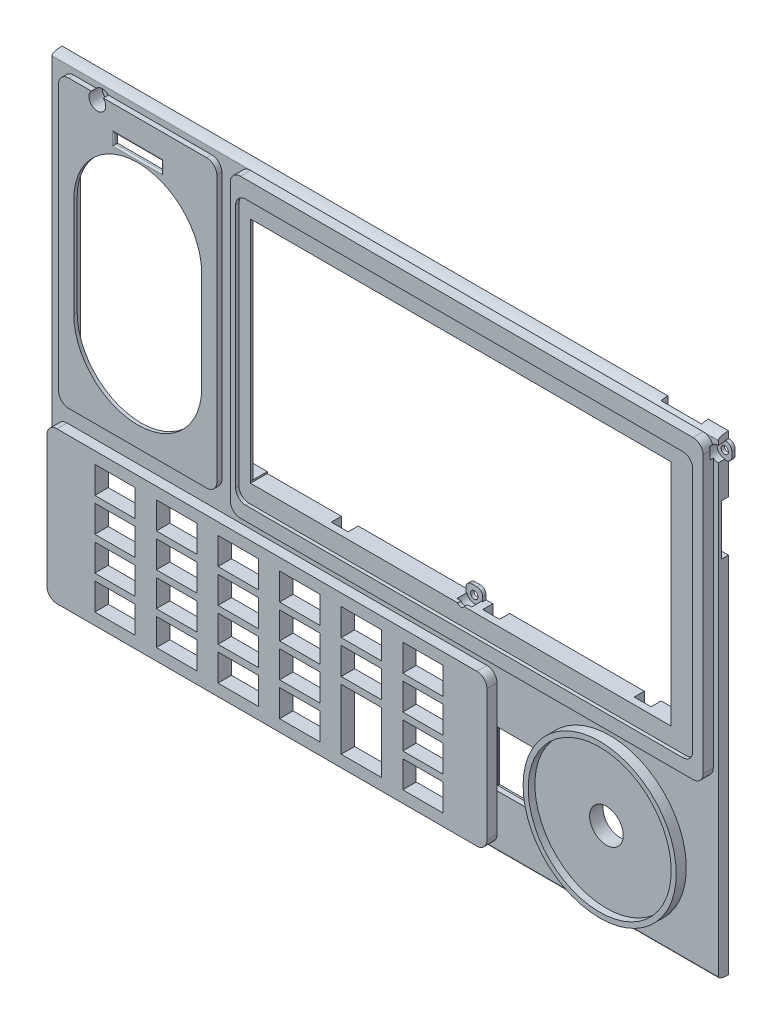
SolidWorks part; units mm, degrees
ref_plane "Front Plane" through (0, 0, 0) normal (0, 0, 1) x (1, 0, 0)
ref_plane "Top Plane" through (0, 0, 0) normal (0, 1, 0) x (1, 0, 0)
ref_plane "Right Plane" through (0, 0, 0) normal (1, 0, 0) x (0, 0, -1)
sketch "Sketch1" plane through (0, 0, 0) normal (0, 0, 1) x (1, 0, 0)
  line L1 (99, -70) -> (-99, -70)
  line L2 (99, -70) -> (99, 70)
  line L3 (99, 70) -> (-99, 70)
  line L4 (-99, -70) -> (-99, 70)
  line L5 (99, -70) -> (-99, 70) construction
  line L6 (99, 70) -> (-99, -70) construction
  point P0 (0, 0)
  dimension "D1" = 198
  dimension "D2" = 140
extrude "main_body" add sketch "Sketch1" along normal blind 3
fillet "long_corners" radius 3 2 edges at (0, 70, 3) (0, -70, 3) second distance 1 first distance on face at (0, 70, 1.5) first distance on face at (0, -70, 1.5)
sketch "Sketch2" plane through (0, 0, 3) normal (0, 0, 1) x (1, 0, 0)
  line L0 (-99, 24.75) -> (99, 24.75) construction
  line L1 (-99, 69) -> (-99, -69) construction
  line L2 (99, -69) -> (99, 69) construction
  line L3 (99, 69) -> (-99, 69) construction
  line L4 (-48.5, -17.75) -> (-95.5, -17.75)
  line L5 (-48.5, -17.75) -> (-48.5, 67.25)
  line L6 (-48.5, 67.25) -> (-95.5, 67.25)
  line L7 (-95.5, -17.75) -> (-95.5, 67.25)
  line L8 (-48.5, -17.75) -> (-95.5, 67.25) construction
  line L9 (-48.5, 67.25) -> (-95.5, -17.75) construction
  point P6 (-72, 24.75)
  dimension "D1" = 85
  dimension "D2" = 47
  dimension "D3" = 27
  dimension "D4" = 44.25
extrude "speaker" add sketch "Sketch2" along normal blind 1.5
fillet "speaker_corners" radius 3 4 edges at (-95.5, 67.25, 3.75) (-95.5, -17.75, 3.75) (-48.5, -17.75, 3.75) (-48.5, 67.25, 3.75)
sketch "Sketch19" plane through (0, 0, 4.5) normal (0, 0, 1) x (1, 0, 0)
  line L0 (-72, 67.25) -> (-72, -17.75) construction
  line L1 (-51.5, 67.25) -> (-92.5, 67.25) construction
  line L2 (-92.5, -17.75) -> (-51.5, -17.75) construction
  line L3 (-72, 7.25) -> (-72, 36.75) construction
  line L4 (-95.5, 64.25) -> (-95.5, -14.75) construction
  line L5 (-95.5, 24.75) -> (-48.5, 24.75) construction
  line L6 (-48.5, -14.75) -> (-48.5, 64.25) construction
  line L7 (-91, 7.25) -> (-91, 36.75)
  line L8 (-53, 7.25) -> (-53, 36.75)
  arc A0 (-91, 7.25) -> (-53, 7.25) centre (-72, 7.25) ccw
  arc A1 (-53, 36.75) -> (-91, 36.75) centre (-72, 36.75) ccw
  point P14 (-72, 22)
  point P19 (-72, -11.75)
  point P20 (-72, 55.75)
  dimension "D2" = 67.5
  dimension "D1" = 38
  dimension "D3" = 11.5
  dimension "D4" = 6
extrude "speaker_cut" cut sketch "Sketch19" against normal through all
sketch "Sketch21" plane through (0, 0, 0) normal (0, 0, -1) x (-1, 0, 0)
  line L0 (72, -11.75) -> (72, 55.75) construction
  line L2 (53, 7.25) -> (53, 36.75) construction
  line L3 (53, 22) -> (91, 22) construction
  line L4 (91, 36.75) -> (91, 7.25) construction
  line L5 (50.5, 61) -> (93.5, 61)
  line L6 (50.5, 61) -> (50.5, -17)
  line L7 (50.5, -17) -> (93.5, -17)
  line L8 (93.5, 61) -> (93.5, -17)
  line L9 (50.5, 61) -> (93.5, -17) construction
  line L10 (50.5, -17) -> (93.5, 61) construction
  arc A0 (53, 7.25) -> (91, 7.25) centre (72, 7.25) ccw construction
  arc A1 (91, 36.75) -> (53, 36.75) centre (72, 36.75) ccw construction
  point P14 (72, 22)
  dimension "D1" = 43
  dimension "D2" = 78
extrude "speaker_slot" cut sketch "Sketch21" against normal blind 3.5
sketch "Sketch3" plane through (0, 0, 3) normal (0, 0, 1) x (1, 0, 0)
  line L0 (-99, 25) -> (99, 25) construction
  line L1 (-99, 69) -> (-99, -69) construction
  line L2 (99, -69) -> (99, 69) construction
  line L4 (-48.5, -14.75) -> (-48.5, 64.25) construction
  line L5 (97.5, -19) -> (-43, -19)
  line L6 (97.5, -19) -> (97.5, 69)
  line L7 (97.5, 69) -> (-43, 69)
  line L8 (-43, -19) -> (-43, 69)
  line L9 (97.5, -19) -> (-43, 69) construction
  line L10 (97.5, 69) -> (-43, -19) construction
  line L11 (99, 70) -> (-99, 70) construction
  point P8 (27.25, 25)
  dimension "D1" = 1
  dimension "D2" = 88
  dimension "D3" = 140.5
  dimension "D4" = 1.5
  dimension "D5" = 5.5
extrude "lcd" add sketch "Sketch3" along normal blind 3
fillet "lcd_corners" radius 3 4 edges at (97.5, -19, 4.5) (-43, -19, 4.5)
sketch "Sketch9" plane through (0, 0, 6) normal (0, 0, 1) x (1, 0, 0)
  line L0 (-43, 24.5) -> (97.5, 24.5) construction
  line L1 (-43, 66) -> (-43, -16) construction
  line L2 (97.5, -16) -> (97.5, 66) construction
  line L3 (-40, -19) -> (94.5, -19) construction
  line L4 (94.4, -14.875) -> (-41.4, -14.875)
  line L5 (94.4, -14.875) -> (94.4, 63.875)
  line L6 (94.4, 63.875) -> (-41.4, 63.875)
  line L7 (-41.4, -14.875) -> (-41.4, 63.875)
  line L8 (94.4, -14.875) -> (-41.4, 63.875) construction
  line L9 (94.4, 63.875) -> (-41.4, -14.875) construction
  line L10 (94.5, 69) -> (-40, 69) construction
  line L11 (97.5, -16) -> (97.5, 66) construction
  point P6 (26.5, 24.5)
  dimension "D1" = 135.8
  dimension "D2" = 78.75
  dimension "D3" = 1.6
  dimension "D4" = 4.125
  dimension "D5" = 5.125
  dimension "D6" = 3.1
extrude "lcd_front" cut sketch "Sketch9" against normal blind 1
fillet "lcd_front_corners" radius 3 4 edges at (94.4, -14.875, 5.5) (94.4, 63.875, 5.5) (-41.4, 63.875, 5.5) (-41.4, -14.875, 5.5)
sketch "Sketch10" plane through (0, 0, 0) normal (0, 0, -1) x (-1, 0, 0)
  line L0 (-94.4, -11.875) -> (-94.4, 60.875) construction
  line L1 (-91.4, 63.875) -> (38.4, 63.875) construction
  line L2 (41.4, 63.875) -> (41.4, -14.875) construction
  line L3 (-94.4, 63.875) -> (41.4, 63.875) construction
  line L4 (38, -9.5) -> (-87, -9.5)
  line L5 (38, -9.5) -> (38, 58.5)
  line L6 (38, 58.5) -> (-87, 58.5)
  line L7 (-87, -9.5) -> (-87, 58.5)
  line L8 (-87, -9.5) -> (38, 58.5) construction
  line L9 (-87, 58.5) -> (38, -9.5) construction
  line L10 (-99, -70) -> (-99, 70) construction
  line L11 (-99, 70) -> (99, 70) construction
  line L13 (38.4, -14.875) -> (-91.4, -14.875) construction
  dimension "D1" = 125
  dimension "D2" = 68
  dimension "D3" = 12
  dimension "D4" = 3.4
  dimension "D5" = 11.5
  dimension "D6" = 5.375
  dimension "D7" = 7.4
  dimension "D8" = 5.375
  dimension "D9" = 5.375
extrude "lcd_back" cut sketch "Sketch10" against normal through all
sketch "Sketch56" plane through (0, 0, 0) normal (0, 0, -1) x (-1, 0, 0)
  line L0 (-87, -9.5) -> (38, -9.5) construction
  line L1 (-79, -9.5) -> (-74, -9.5)
  line L2 (-79, -9.5) -> (-79, -12.5)
  line L3 (-79, -12.5) -> (-74, -12.5)
  line L4 (-74, -9.5) -> (-74, -12.5)
  line L5 (38, 58.5) -> (-87, 58.5) construction
  line L6 (-34, -9.5) -> (-29, -9.5)
  line L7 (-34, -9.5) -> (-34, -12.5)
  line L8 (-34, -12.5) -> (-29, -12.5)
  line L9 (-29, -9.5) -> (-29, -12.5)
  line L10 (11, -9.5) -> (16, -9.5)
  line L11 (11, -9.5) -> (11, -12.5)
  line L12 (11, -12.5) -> (16, -12.5)
  line L13 (16, -9.5) -> (16, -12.5)
  line L14 (-79, 58.5) -> (-74, 58.5)
  line L15 (-79, 58.5) -> (-79, 61.5)
  line L16 (-79, 61.5) -> (-74, 61.5)
  line L17 (-74, 58.5) -> (-74, 61.5)
  line L18 (38, -9.5) -> (38, 58.5) construction
  line L19 (-34, 58.5) -> (-29, 58.5)
  line L20 (-34, 58.5) -> (-34, 61.5)
  line L21 (-34, 61.5) -> (-29, 61.5)
  line L22 (-29, 58.5) -> (-29, 61.5)
  line L23 (11, 58.5) -> (16, 58.5)
  line L24 (11, 58.5) -> (11, 61.5)
  line L25 (11, 61.5) -> (16, 61.5)
  line L26 (16, 58.5) -> (16, 61.5)
  line L27 (38, 58) -> (42, 58)
  line L28 (38, 58) -> (38, -9)
  line L29 (38, -9) -> (42, -9)
  line L30 (42, 58) -> (42, -9)
  line L31 (-99, -70) -> (-99, 70) construction
  line L32 (-99, 70) -> (99, 70) construction
  point P34 (-29, -11)
  dimension "D1" = 5
  dimension "D2" = 5
  dimension "D3" = 5
  dimension "D4" = 5
  dimension "D5" = 5
  dimension "D6" = 5
  dimension "D7" = 67
  dimension "D8" = 4
  dimension "D9" = 3
  dimension "D10" = 3
  dimension "D11" = 3
  dimension "D12" = 3
  dimension "D13" = 3
  dimension "D14" = 3
  dimension "D15" = 40
  dimension "D16" = 40
  dimension "D17" = 20
  dimension "D18" = 20
  dimension "D19" = 40
  dimension "D20" = 40
  dimension "D21" = 12
extrude "lcd_glue_points" cut sketch "Sketch56" against normal blind 3
sketch "Sketch4" plane through (0, 0, 3) normal (0, 0, 1) x (1, 0, 0)
  line L0 (-99, -45.75) -> (99, -45.75) construction
  line L1 (-99, 69) -> (-99, -69) construction
  line L2 (99, -69) -> (99, 69) construction
  line L4 (-92.5, -17.75) -> (-51.5, -17.75) construction
  line L5 (33.25, -68.25) -> (-97.5, -68.25)
  line L6 (33.25, -68.25) -> (33.25, -23.25)
  line L7 (33.25, -23.25) -> (-97.5, -23.25)
  line L8 (-97.5, -68.25) -> (-97.5, -23.25)
  line L9 (33.25, -68.25) -> (-97.5, -23.25) construction
  line L10 (33.25, -23.25) -> (-97.5, -68.25) construction
  line L11 (-99, -70) -> (99, -70) construction
  point P8 (-32.125, -45.75)
  dimension "D1" = 1.75
  dimension "D2" = 130.75
  dimension "D3" = 45
  dimension "D4" = 1.5
  dimension "D5" = 5.5
extrude "keypad" add sketch "Sketch4" along normal blind 3
fillet "keypad_corners" radius 3 4 edges at (-97.5, -68.25, 4.5) (33.25, -68.25, 4.5) (33.25, -23.25, 4.5) (-97.5, -23.25, 4.5)
sketch "Sketch25" plane through (0, 0, 6) normal (0, 0, 1) x (1, 0, 0)
  line L0 (-97.5, -30.75) -> (33.25, -30.75) construction
  line L1 (30.25, -23.25) -> (-94.5, -23.25) construction
  line L2 (-94.5, -68.25) -> (30.25, -68.25) construction
  line L3 (-77.25, -23.25) -> (-77.25, -68.25) construction
  line L5 (-34.65, -64.75) -> (33.25, -64.75) construction
  line L6 (-97.5, -26.25) -> (-97.5, -65.25) construction
  line L11 (33.25, -65.25) -> (33.25, -26.25) construction
  line L12 (-58.95, -23.25) -> (-58.95, -68.25) construction
  line L13 (-97.5, -40.75) -> (33.25, -40.75) construction
  line L14 (30.25, -23.25) -> (-94.5, -23.25) construction
  line L15 (-40.65, -23.25) -> (-40.65, -68.25) construction
  line L16 (-94.5, -68.25) -> (30.25, -68.25) construction
  line L17 (-71.25, -34.75) -> (-83.25, -34.75)
  line L18 (-22.35, -23.25) -> (-22.35, -68.25) construction
  line L19 (-97.5, -50.75) -> (33.25, -50.75) construction
  line L20 (-4.05, -23.25) -> (-4.05, -68.25) construction
  line L21 (-71.25, -34.75) -> (-71.25, -26.75)
  line L22 (14.25, -23.25) -> (14.25, -68.25) construction
  line L23 (-97.5, -26.25) -> (-97.5, -65.25) construction
  line L24 (-97.5, -60.75) -> (33.25, -60.75) construction
  line L25 (-71.25, -26.75) -> (-83.25, -26.75)
  line L26 (-83.25, -34.75) -> (-83.25, -26.75)
  line L27 (-71.25, -34.75) -> (-83.25, -26.75) construction
  line L28 (-71.25, -26.75) -> (-83.25, -34.75) construction
  line L29 (-71.25, -44.75) -> (-83.25, -44.75)
  line L30 (-71.25, -44.75) -> (-71.25, -36.75)
  line L31 (-71.25, -36.75) -> (-83.25, -36.75)
  line L32 (-83.25, -44.75) -> (-83.25, -36.75)
  line L33 (-71.25, -44.75) -> (-83.25, -36.75) construction
  line L34 (-71.25, -36.75) -> (-83.25, -44.75) construction
  line L35 (-71.25, -54.75) -> (-83.25, -54.75)
  line L36 (-71.25, -54.75) -> (-71.25, -46.75)
  line L37 (-71.25, -46.75) -> (-83.25, -46.75)
  line L38 (-83.25, -54.75) -> (-83.25, -46.75)
  line L39 (-71.25, -54.75) -> (-83.25, -46.75) construction
  line L40 (-71.25, -46.75) -> (-83.25, -54.75) construction
  line L41 (-71.25, -64.75) -> (-83.25, -64.75)
  line L42 (-71.25, -64.75) -> (-71.25, -56.75)
  line L43 (-71.25, -56.75) -> (-83.25, -56.75)
  line L44 (-83.25, -64.75) -> (-83.25, -56.75)
  line L45 (-71.25, -64.75) -> (-83.25, -56.75) construction
  line L46 (-71.25, -56.75) -> (-83.25, -64.75) construction
  line L47 (-52.95, -34.75) -> (-64.95, -34.75)
  line L48 (-52.95, -34.75) -> (-52.95, -26.75)
  line L49 (-52.95, -26.75) -> (-64.95, -26.75)
  line L50 (-64.95, -34.75) -> (-64.95, -26.75)
  line L51 (-52.95, -34.75) -> (-64.95, -26.75) construction
  line L52 (-52.95, -26.75) -> (-64.95, -34.75) construction
  line L53 (-52.95, -44.75) -> (-64.95, -44.75)
  line L54 (-52.95, -44.75) -> (-52.95, -36.75)
  line L55 (-52.95, -36.75) -> (-64.95, -36.75)
  line L56 (-64.95, -44.75) -> (-64.95, -36.75)
  line L57 (-52.95, -44.75) -> (-64.95, -36.75) construction
  line L58 (-52.95, -36.75) -> (-64.95, -44.75) construction
  line L59 (-52.95, -54.75) -> (-64.95, -54.75)
  line L60 (-52.95, -54.75) -> (-52.95, -46.75)
  line L61 (-52.95, -46.75) -> (-64.95, -46.75)
  line L62 (-64.95, -54.75) -> (-64.95, -46.75)
  line L63 (-52.95, -54.75) -> (-64.95, -46.75) construction
  line L64 (-52.95, -46.75) -> (-64.95, -54.75) construction
  line L65 (-52.95, -64.75) -> (-64.95, -64.75)
  line L66 (-52.95, -64.75) -> (-52.95, -56.75)
  line L67 (-52.95, -56.75) -> (-64.95, -56.75)
  line L68 (-64.95, -64.75) -> (-64.95, -56.75)
  line L69 (-52.95, -64.75) -> (-64.95, -56.75) construction
  line L70 (-52.95, -56.75) -> (-64.95, -64.75) construction
  line L71 (-34.65, -34.75) -> (-46.65, -34.75)
  line L72 (-34.65, -34.75) -> (-34.65, -26.75)
  line L73 (-34.65, -26.75) -> (-46.65, -26.75)
  line L74 (-46.65, -34.75) -> (-46.65, -26.75)
  line L75 (-34.65, -34.75) -> (-46.65, -26.75) construction
  line L76 (-34.65, -26.75) -> (-46.65, -34.75) construction
  line L77 (-34.65, -44.75) -> (-46.65, -44.75)
  line L78 (-34.65, -44.75) -> (-34.65, -36.75)
  line L79 (-34.65, -36.75) -> (-46.65, -36.75)
  line L80 (-46.65, -44.75) -> (-46.65, -36.75)
  line L81 (-34.65, -44.75) -> (-46.65, -36.75) construction
  line L82 (-34.65, -36.75) -> (-46.65, -44.75) construction
  line L83 (-34.65, -54.75) -> (-46.65, -54.75)
  line L84 (-34.65, -54.75) -> (-34.65, -46.75)
  line L85 (-34.65, -46.75) -> (-46.65, -46.75)
  line L86 (-46.65, -54.75) -> (-46.65, -46.75)
  line L87 (-34.65, -54.75) -> (-46.65, -46.75) construction
  line L88 (-34.65, -46.75) -> (-46.65, -54.75) construction
  line L89 (-34.65, -64.75) -> (-46.65, -64.75)
  line L90 (-34.65, -64.75) -> (-34.65, -56.75)
  line L91 (-34.65, -56.75) -> (-46.65, -56.75)
  line L92 (-46.65, -64.75) -> (-46.65, -56.75)
  line L93 (-34.65, -64.75) -> (-46.65, -56.75) construction
  line L94 (-34.65, -56.75) -> (-46.65, -64.75) construction
  line L95 (-16.35, -34.75) -> (-28.35, -34.75)
  line L96 (-16.35, -34.75) -> (-16.35, -26.75)
  line L97 (-16.35, -26.75) -> (-28.35, -26.75)
  line L98 (-28.35, -34.75) -> (-28.35, -26.75)
  line L99 (-16.35, -34.75) -> (-28.35, -26.75) construction
  line L100 (-16.35, -26.75) -> (-28.35, -34.75) construction
  line L101 (-16.35, -44.75) -> (-28.35, -44.75)
  line L102 (-16.35, -44.75) -> (-16.35, -36.75)
  line L103 (-16.35, -36.75) -> (-28.35, -36.75)
  line L104 (-28.35, -44.75) -> (-28.35, -36.75)
  line L105 (-16.35, -44.75) -> (-28.35, -36.75) construction
  line L106 (-16.35, -36.75) -> (-28.35, -44.75) construction
  line L111 (-16.35, -54.75) -> (-28.35, -54.75)
  line L112 (-16.35, -54.75) -> (-16.35, -46.75)
  line L113 (-16.35, -46.75) -> (-28.35, -46.75)
  line L114 (-28.35, -54.75) -> (-28.35, -46.75)
  line L115 (-16.35, -54.75) -> (-28.35, -46.75) construction
  line L116 (-16.35, -46.75) -> (-28.35, -54.75) construction
  line L117 (-16.35, -64.75) -> (-28.35, -64.75)
  line L118 (-16.35, -64.75) -> (-16.35, -56.75)
  line L119 (-16.35, -56.75) -> (-28.35, -56.75)
  line L120 (-28.35, -64.75) -> (-28.35, -56.75)
  line L121 (-16.35, -64.75) -> (-28.35, -56.75) construction
  line L122 (-16.35, -56.75) -> (-28.35, -64.75) construction
  line L127 (1.95, -34.75) -> (-10.05, -34.75)
  line L128 (1.95, -34.75) -> (1.95, -26.75)
  line L129 (1.95, -26.75) -> (-10.05, -26.75)
  line L130 (-10.05, -34.75) -> (-10.05, -26.75)
  line L131 (1.95, -34.75) -> (-10.05, -26.75) construction
  line L132 (1.95, -26.75) -> (-10.05, -34.75) construction
  line L133 (20.25, -34.75) -> (8.25, -34.75)
  line L134 (20.25, -34.75) -> (20.25, -26.75)
  line L135 (20.25, -26.75) -> (8.25, -26.75)
  line L136 (8.25, -34.75) -> (8.25, -26.75)
  line L137 (20.25, -34.75) -> (8.25, -26.75) construction
  line L138 (20.25, -26.75) -> (8.25, -34.75) construction
  line L139 (1.95, -44.75) -> (-10.05, -44.75)
  line L140 (1.95, -44.75) -> (1.95, -36.75)
  line L141 (1.95, -36.75) -> (-10.05, -36.75)
  line L142 (-10.05, -44.75) -> (-10.05, -36.75)
  line L143 (1.95, -44.75) -> (-10.05, -36.75) construction
  line L144 (1.95, -36.75) -> (-10.05, -44.75) construction
  line L145 (20.25, -44.75) -> (8.25, -44.75)
  line L146 (20.25, -44.75) -> (20.25, -36.75)
  line L147 (20.25, -36.75) -> (8.25, -36.75)
  line L148 (8.25, -44.75) -> (8.25, -36.75)
  line L149 (20.25, -44.75) -> (8.25, -36.75) construction
  line L150 (20.25, -36.75) -> (8.25, -44.75) construction
  line L151 (20.25, -54.75) -> (8.25, -54.75)
  line L152 (20.25, -54.75) -> (20.25, -46.75)
  line L153 (20.25, -46.75) -> (8.25, -46.75)
  line L154 (8.25, -54.75) -> (8.25, -46.75)
  line L155 (20.25, -54.75) -> (8.25, -46.75) construction
  line L156 (20.25, -46.75) -> (8.25, -54.75) construction
  line L157 (20.25, -64.75) -> (8.25, -64.75)
  line L158 (20.25, -64.75) -> (20.25, -56.75)
  line L159 (20.25, -56.75) -> (8.25, -56.75)
  line L160 (8.25, -64.75) -> (8.25, -56.75)
  line L161 (20.25, -64.75) -> (8.25, -56.75) construction
  line L162 (20.25, -56.75) -> (8.25, -64.75) construction
  line L163 (1.95, -64.75) -> (-10.05, -64.75)
  line L164 (1.95, -64.75) -> (1.95, -46.75)
  line L165 (1.95, -46.75) -> (-10.05, -46.75)
  line L166 (-10.05, -64.75) -> (-10.05, -46.75)
  line L167 (1.95, -64.75) -> (-10.05, -46.75) construction
  line L168 (1.95, -46.75) -> (-10.05, -64.75) construction
  point P34 (-77.25, -30.75)
  point P39 (-77.25, -40.75)
  point P44 (-77.25, -50.75)
  point P49 (-77.25, -60.75)
  point P54 (-58.95, -30.75)
  point P59 (-58.95, -40.75)
  point P64 (-58.95, -50.75)
  point P69 (-58.95, -60.75)
  point P74 (-40.65, -30.75)
  point P79 (-40.65, -40.75)
  point P84 (-40.65, -50.75)
  point P89 (-40.65, -60.75)
  point P94 (-22.35, -30.75)
  point P99 (-22.35, -40.75)
  point P104 (-22.35, -50.75)
  point P109 (-22.35, -60.75)
  point P114 (-4.05, -30.75)
  point P119 (14.25, -30.75)
  point P124 (-4.05, -40.75)
  point P129 (14.25, -40.75)
  point P134 (14.25, -50.75)
  point P139 (14.25, -60.75)
  point P144 (-4.05, -55.75)
  dimension "D1" = 19
  dimension "D2" = 18.3
  dimension "D3" = 18.3
  dimension "D4" = 18.3
  dimension "D5" = 18.3
  dimension "D6" = 18.3
  dimension "D7" = 20.25
  dimension "D8" = 7.5
  dimension "D9" = 10
  dimension "D10" = 10
  dimension "D11" = 10
  dimension "D12" = 7.5
  dimension "D13" = 12
  dimension "D14" = 12
  dimension "D15" = 12
  dimension "D16" = 12
  dimension "D17" = 12
  dimension "D18" = 12
  dimension "D19" = 12
  dimension "D20" = 12
  dimension "D21" = 12
  dimension "D22" = 12
  dimension "D23" = 12
  dimension "D24" = 12
  dimension "D25" = 12
  dimension "D26" = 12
  dimension "D27" = 12
  dimension "D28" = 12
  dimension "D29" = 12
  dimension "D30" = 12
  dimension "D31" = 12
  dimension "D32" = 12
  dimension "D33" = 12
  dimension "D34" = 12
  dimension "D35" = 12
  dimension "D36" = 8
  dimension "D37" = 8
  dimension "D38" = 8
  dimension "D39" = 8
  dimension "D40" = 8
  dimension "D41" = 8
  dimension "D42" = 18
  dimension "D43" = 8
  dimension "D44" = 8
  dimension "D45" = 8
  dimension "D46" = 8
  dimension "D47" = 8
  dimension "D48" = 8
  dimension "D49" = 8
  dimension "D50" = 8
  dimension "D51" = 8
  dimension "D52" = 8
  dimension "D53" = 8
  dimension "D54" = 8
  dimension "D55" = 8
  dimension "D56" = 8
  dimension "D57" = 8
  dimension "D58" = 8
  dimension "D59" = 5
extrude "keypad_cuts_0.8" cut sketch "Sketch25" against normal through all
sketch "Sketch5" plane through (0, 0, 3) normal (0, 0, 1) x (1, 0, 0)
  line L0 (33.25, -45.75) -> (99, -45.75) construction
  line L1 (33.25, -65.25) -> (33.25, -26.25) construction
  line L2 (99, -69) -> (99, 69) construction
  circle A0 centre (66.75, -45.75) radius 22.75
  dimension "D1" = 45.5
  dimension "D2" = 32.25
  dimension "D3" = 33.5
extrude "vfo" add sketch "Sketch5" along normal blind 3
sketch "Sketch7" plane through (0, 0, 6) normal (0, 0, 1) x (1, 0, 0)
  line L0 (44, -45.75) -> (89.5, -45.75) construction
  line L1 (66.75, -23) -> (66.75, -68.5) construction
  circle A0 centre (66.75, -45.75) radius 22.75 construction
  circle A1 centre (66.75, -45.75) radius 22.75 construction
  circle A2 centre (66.75, -45.75) radius 5
  dimension "D1" = 10
extrude "vfo_encoder_knob_cut" cut sketch "Sketch7" against normal through all
sketch "esp32" plane through (0, 0, 0) normal (0, 0, -1) x (-1, 0, 0)
  line L0 (99, -70) -> (-99, -70) construction
  line L1 (-50.5, -37.5) -> (-32, -37.5)
  line L2 (-50.5, -37.5) -> (-50.5, -54)
  line L3 (-50.5, -54) -> (-32, -54)
  line L4 (-32, -37.5) -> (-32, -54)
  line L5 (-99, -70) -> (-99, 70) construction
  dimension "D1" = 16
  dimension "D2" = 48.5
  dimension "D3" = 16.5
  dimension "D4" = 18.5
extrude "esp32_can_cut" cut sketch "esp32" against normal blind 3
sketch "Sketch47" plane through (0, 0, 0) normal (0, 0, -1) x (-1, 0, 0)
  line L0 (-50.5, -54) -> (-32, -54) construction
  line L1 (-31, -55) -> (-58, -55)
  line L2 (-31, -55) -> (-31, -36.5)
  line L3 (-31, -36.5) -> (-58, -36.5)
  line L4 (-58, -55) -> (-58, -36.5)
  line L5 (-31, -55) -> (-58, -36.5) construction
  line L6 (-31, -36.5) -> (-58, -55) construction
  line L7 (-50.5, -37.5) -> (-50.5, -54) construction
  point P0 (-44.5, -45.75)
  dimension "D1" = 27
  dimension "D2" = 18.5
  dimension "D3" = 1
  dimension "D4" = 7.5
extrude "esp32_ex_cut" cut sketch "Sketch47" against normal blind 1.5
sketch "Sketch49" plane through (0, 0, 0) normal (0, 0, -1) x (-1, 0, 0)
  line L0 (72, 58.25) -> (72, 67.25) construction
  line L3 (51.5, 67.25) -> (92.5, 67.25) construction
  line L4 (79, 56.75) -> (65, 56.75)
  line L5 (79, 56.75) -> (79, 59.75)
  line L6 (79, 59.75) -> (65, 59.75)
  line L7 (65, 56.75) -> (65, 59.75)
  line L8 (79, 56.75) -> (65, 59.75) construction
  line L9 (79, 59.75) -> (65, 56.75) construction
  point P6 (72, 58.25)
  dimension "D1" = 14
  dimension "D2" = 3
  dimension "D3" = 9
extrude "amb_sensor" cut sketch "Sketch49" against normal through all
fillet "amb_corners" radius 0.5 4 edges at (-65, 58.25, 4.5) (-72, 59.75, 4.5) (-79, 58.25, 4.5) (-72, 56.75, 4.5)
sketch "Sketch55" plane through (0, 0, 0) normal (0, 0, -1) x (-1, 0, 0)
  line L0 (-99, -70) -> (-99, 70) construction
  line L5 (-93, 70) -> (-81, 70)
  line L6 (-93, 70) -> (-93, 58.5)
  line L11 (-93, 58.5) -> (-81, 58.5)
  line L12 (-81, 70) -> (-81, 58.5)
  line L13 (94.5, 48) -> (99, 48)
  line L14 (94.5, 48) -> (94.5, 33)
  line L15 (94.5, 33) -> (99, 33)
  line L16 (99, 48) -> (99, 33)
  line L17 (94.5, 48) -> (99, 33) construction
  line L18 (94.5, 33) -> (99, 48) construction
  line L23 (99, 65.5) -> (-99, 65.5) construction
  line L24 (99, -8.5) -> (-99, -8.5) construction
  line L35 (-99, -68) -> (99, -68) construction
  line L36 (99, -70) -> (-99, -70) construction
  line L42 (-99, 53) -> (-93, 53)
  line L43 (-99, 53) -> (-99, 38)
  line L44 (-99, 70) -> (99, 70) construction
  line L45 (-99, 38) -> (-93, 38)
  line L46 (99, 70) -> (99, -70) construction
  line L47 (-93, 53) -> (-93, 38)
  circle A1 centre (49.5, 65.5) radius 3
  circle A2 centre (-24.5, 65.5) radius 3
  circle A4 centre (49.5, -8.5) radius 3
  circle A6 centre (-68, -68) radius 3
  circle A7 centre (-1, -68) radius 3
  circle A9 centre (-32, 65.5) radius 3
  point P10 (96.75, 40.5)
  point P25 (0, 0)
  dimension "D8" = 6
  dimension "D9" = 6
  dimension "D13" = 6
  dimension "D18" = 2
  dimension "D19" = 6
  dimension "D21" = 6
  dimension "D22" = 6
  dimension "D1" = 12
  dimension "D3" = 11.5
  dimension "D4" = 0
  dimension "D5" = 6
  dimension "D6" = 4.5
  dimension "D11" = 49.5
  dimension "D12" = 123.5
  dimension "D14" = 7.5
  dimension "D15" = 61.5
  dimension "D24" = 100
  dimension "D25" = 15
  dimension "D26" = 4.5
  dimension "D27" = 0
  dimension "D28" = 22
  dimension "D29" = 49.5
  dimension "D30" = 67
  dimension "D31" = 6
  dimension "D32" = 15
  dimension "D33" = 0
  dimension "D34" = 17
extrude "conn_cutouts" cut sketch "Sketch55" against normal blind 2
fillet "Fillet1" radius 2 1 edges at (-38, 24.5, 3)
fillet "Fillet2" radius 5 1 edges at (-42, 24.5, 0)
sketch "Sketch57" plane through (0, 0, 0) normal (0, 0, -1) x (-1, 0, 0)
  line L0 (99, 70) -> (99, 48) construction
  line L1 (-24, -22) -> (89, -22)
  line L2 (-24, -22) -> (-24, -67.5)
  line L3 (-24, -67.5) -> (89, -67.5)
  line L4 (89, -22) -> (89, -67.5)
  line L5 (99, -70) -> (1.2361, -70) construction
  dimension "D1" = 113
  dimension "D2" = 45.5
  dimension "D3" = 10
  dimension "D4" = 2.5
extrude "keyboard_back" cut sketch "Sketch57" against normal blind 2
sketch "Sketch58" plane through (0, -9.5, 0) normal (0, 1, 0) x (1, 0, 0)
  line L1 (27, -1) -> (22, -1)
  line L2 (27, -1) -> (27, 0)
  line L3 (27, 0) -> (22, 0)
  line L4 (22, -1) -> (22, 0)
  line L5 (27, -1) -> (22, 0) construction
  line L6 (27, 0) -> (22, -1) construction
  line L7 (29, -3) -> (29, 0) construction
  line L9 (29, 0) -> (-11, 0) construction
  point P0 (24.5, -0.5)
  dimension "D1" = 1
  dimension "D2" = 5
  dimension "D3" = 2
  dimension "D4" = 0
extrude "behind_lcd_screew_mount" add sketch "Sketch58" along normal blind 3
sketch "Sketch59" plane through (-99, 0, 0) normal (-1, 0, 0) x (0, 0, 1)
  line L0 (0, 70) -> (0, 48) construction
  line L1 (0, -66.5) -> (1, -66.5)
  line L2 (0, -66.5) -> (0, -69.5)
  line L3 (0, -69.5) -> (1, -69.5)
  line L4 (1, -66.5) -> (1, -69.5)
  dimension "D1" = 1
  dimension "D2" = 3
  dimension "D3" = 66.5
extrude "keyb_screw_mount" add sketch "Sketch59" along normal blind 1
sketch "Sketch60" plane through (99, 0, 0) normal (1, 0, 0) x (0, 0, -1)
  line L0 (0, -70) -> (0, 38) construction
  line L1 (0, 68) -> (-1, 68)
  line L2 (0, 68) -> (0, 63)
  line L3 (0, 63) -> (-1, 63)
  line L4 (-1, 68) -> (-1, 63)
  dimension "D1" = 63
  dimension "D2" = 5
  dimension "D3" = 1
extrude "right_corner_screw_mount" add sketch "Sketch60" along normal blind 2
sketch "Sketch61" plane through (0, 0, 0) normal (0, 0, -1) x (-1, 0, 0)
  line L0 (-99, 70) -> (-93, 70) construction
  line L1 (-99, 68) -> (-99, 70) construction
  line L2 (-99, -9) -> (99, -9) construction
  line L3 (99, 70) -> (99, 48) construction
  line L5 (-99, -70) -> (-99, 38) construction
  line L6 (99, 70) -> (99, 48) construction
  line L7 (-3.2361, -70) -> (-65.7639, -70) construction
  line L8 (99, -69.5) -> (99, -70) construction
  line L9 (99, -70) -> (1.2361, -70) construction
  line L10 (-81, 70) -> (99, 70) construction
  circle A0 centre (-98.9, 65.5) radius 1.1
  circle A1 centre (-24.5, -9) radius 1.1
  circle A2 centre (98, -68) radius 1.1
  circle A3 centre (84, 65.5) radius 1.1
  point P26 (0, 0)
  point P28 (92.1614, 70)
  dimension "D1" = 2.2
  dimension "D6" = 2.2
  dimension "D9" = 2.2
  dimension "D10" = 2.2
  dimension "D2" = 4.5
  dimension "D3" = 0.1
  dimension "D4" = 61
  dimension "D5" = 123.5
  dimension "D7" = 1
  dimension "D8" = 2
  dimension "D11" = 15
  dimension "D12" = 4.5
extrude "ui_screws" cut sketch "Sketch61" against normal through all
sketch "Sketch62" plane through (0, 0, 6) normal (0, 0, 1) x (1, 0, 0)
  line L0 (97.8, 65.5) -> (100, 65.5) construction
  line L1 (-98, -66.9) -> (-98, -69.1) construction
  line L2 (98.9, 66.6) -> (98.9, 64.4) construction
  line L4 (-96.9, -68) -> (-99.1, -68) construction
  circle A0 centre (24.5, -9) radius 2.25
  arc A1 (99, 66.5954) -> (99, 64.4046) centre (98.9, 65.5) ccw construction
  arc A2 (99, 64.4046) -> (99, 66.5954) centre (98.9, 65.5) ccw construction
  circle A3 centre (98.9, 65.5) radius 2.25
  arc A4 (-97.5417, -69) -> (-99, -67.5417) centre (-98, -68) ccw construction
  arc A5 (-98.4583, -69) -> (-97.5417, -69) centre (-98, -68) ccw construction
  arc A6 (-99, -67.5417) -> (-99, -68.4583) centre (-98, -68) ccw construction
  circle A7 centre (-98, -68) radius 2.25
  dimension "D1" = 4.5
  dimension "D2" = 4.5
  dimension "D3" = 4.5
extrude "ui_screw_head" cut sketch "Sketch62" against normal blind 3 from offset 2 offset against normal yes
fillet "ui_screw_mount_corners" radius 1.75 6 edges at (-100, -66.5, 0.5) (-100, -69.5, 0.5) (101, 63, 0.5) (101, 68, 0.5) (22, -6.5, 0.5) (27, -6.5, 0.5)
sketch "Sketch63" plane through (0, 0, 6) normal (0, 0, 1) x (1, 0, 0)
  circle A0 centre (66.75, -45.75) radius 21.25
  dimension "D1" = 42.5
extrude "enc_knob_slot" cut sketch "Sketch63" against normal blind 2
sketch "Sketch64" plane through (0, 0, 4.5) normal (0, 0, 1) x (1, 0, 0)
  circle A0 centre (-84, 65.5) radius 2.5
  dimension "D1" = 5
extrude "on_speaker_ui_screw_head" cut sketch "Sketch64" against normal blind 4
